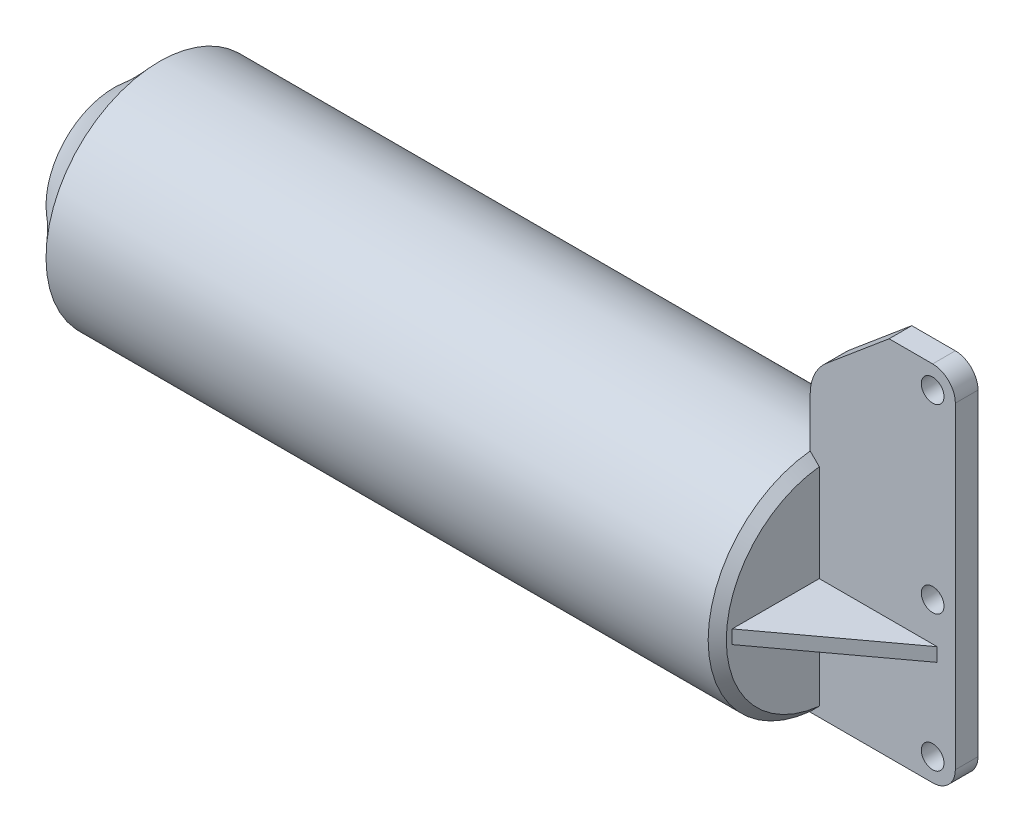
SolidWorks part; units mm, degrees
ref_plane "Front Plane" through (0, 0, 0) normal (0, 0, 1) x (1, 0, 0)
ref_plane "Top Plane" through (0, 0, 0) normal (0, 1, 0) x (1, 0, 0)
ref_plane "Right Plane" through (0, 0, 0) normal (1, 0, 0) x (0, 0, -1)
sketch "Sketch1" plane through (0, 0, 0) normal (1, 0, 0) x (0, 0, -1)
  circle A0 centre (0, 0) radius 12.5
extrude "Boss-Extrude1" add sketch "Sketch1" along normal blind 59
sketch "Sketch2" plane through (0, 0, 0) normal (-1, 0, 0) x (0, 0, 1)
  circle A0 centre (0, 0) radius 7.5
  dimension "D1" = 15
extrude "Boss-Extrude2" add sketch "Sketch2" along normal blind 5
loft "Loft1" add section edge at (0, 0, -12.5) section edge at (-5, 0, 7.5) connector at (0, 6.3089, -10.7911) connector at (-5, 3.7568, -6.4913)
chamfer "Chamfer1" distance 1 angle 45 1 edges at (59, 0, -12.5)
sketch "Sketch3" plane through (0, 0, 0) normal (0, 1, 0) x (1, 0, 0)
  line L0 (0, 0) -> (102.0459, 0) construction
  line L1 (0, 12.5) -> (0, -12.5) construction
  line L2 (59, -11.5) -> (59, 11.5) construction
  line L3 (59, 1.25) -> (74, 1.25)
  line L5 (59, -1.25) -> (74, -1.25)
  line L6 (74, 1.25) -> (74, -1.25)
  line L7 (59, -1.25) -> (58, -1.25)
  line L8 (58, 12.5) -> (58, -12.5) construction
  line L9 (58, -1.25) -> (58, 1.25)
  line L10 (58, 1.25) -> (59, 1.25)
  point P10 (74, 0)
  dimension "D1" = 15
  dimension "D2" = 2.5
extrude "Boss-Extrude3" add sketch "Sketch3" along normal blind 27.5 and the other way blind 12.5
fillet "Fillet1" radius 2.5 2 edges at (74, -12.5, 0) (74, 27.5, 0)
sketch "Sketch4" plane through (0, 0, 1.25) normal (0, 0, 1) x (1, 0, 0)
  circle A0 centre (71.5, -10) radius 1.25
  circle A1 centre (71.5, 25) radius 1.25
  dimension "D1" = 2.5
  dimension "D2" = 2.5
extrude "Cut-Extrude1" cut sketch "Sketch4" against normal blind 27.5
sketch "Sketch5" plane through (0, 0, 1.25) normal (0, 0, 1) x (1, 0, 0)
  line L0 (68.2861, 28.8302) -> (58, 20.1992)
  line L1 (58, 12.4373) -> (58, 27.5) construction
  line L2 (74, -10) -> (74, 25) construction
  line L3 (58, 12.4373) -> (58, 27.5)
  line L4 (58, 27.5) -> (71.5, 27.5) construction
  line L5 (58, 27.5) -> (71.5, 27.5)
  circle A0 centre (71.5, 25) radius 5
  line M8 (71.5, 27.5) -> (58, 27.5)
  line M9 (58, 27.5) -> (58, 12.4373)
  dimension "D2" = 10
  dimension "D1" = 50
extrude "Cut-Extrude2" cut sketch "Sketch5" against normal blind 27.5 contours A0 L0 M8 M9 region at (60.9003, 25.0664, 1.25)
fillet "Fillet2" radius 5 1 edges at (58, 20.1992, 0)
sketch "Sketch6" plane through (0, 0, 1.25) normal (0, 0, 1) x (1, 0, 0)
  circle A0 centre (71.5, 5) radius 1.25
  circle A1 centre (71.5, -10) radius 1.25 construction
  circle A2 centre (71.5, -10) radius 1.25
  dimension "D1" = 2.5
  dimension "D2" = 15
extrude "Cut-Extrude3" cut sketch "Sketch6" against normal blind 27.5
sketch "Sketch7" plane through (0, 0, 0) normal (0, 1, 0) x (1, 0, 0)
  line L0 (59, -10.85) -> (72, -1.25)
  line L1 (59, -11.5) -> (59, -1.25) construction
  line L4 (71.5, -1.25) -> (74, -1.25) construction
  line L5 (66.7008, -1.25) -> (59.7861, -1.25) construction
  dimension "D1" = 13
  dimension "D2" = 9.6
rib "Rib1" sketch "Sketch7" sketch "Sketch7" thickness 1.5 extrusion direction parallel to sketch draft on no parameters "D1"=1.5
mirror "Mirror1" about plane through (0, 0, 0) normal (0, 0, 1) of "Rib1"
sketch "Sketch9" plane through (-5, 0, 0) normal (-1, 0, 0) x (0, 0, 1)
  circle A2 centre (0, 0) radius 12.5 construction
  circle A3 centre (0, 0) radius 12.5
extrude "Boss-Extrude5" add sketch "Sketch9" along normal blind 10 separate body
sketch "Sketch10" plane through (-5, 0, 0) normal (1, 0, 0) x (0, 0, -1)
  circle A0 centre (0, 0) radius 12.5 construction
  circle A1 centre (0, 0) radius 12.5
extrude "Boss-Extrude6" add sketch "Sketch10" along normal blind 10
sketch "Sketch11" plane through (-15, 0, 0) normal (-1, 0, 0) x (0, 0, 1)
  circle A0 centre (0, 0) radius 7.5
  dimension "D1" = 15
extrude "Boss-Extrude7" add sketch "Sketch11" along normal blind 5
loft "Loft2" add section edge at (-15, 0, 12.5) section edge at (-20, 0, 7.5) connector at (-15, 9.9677, -7.5429) connector at (-20, 7.2203, -2.029)
